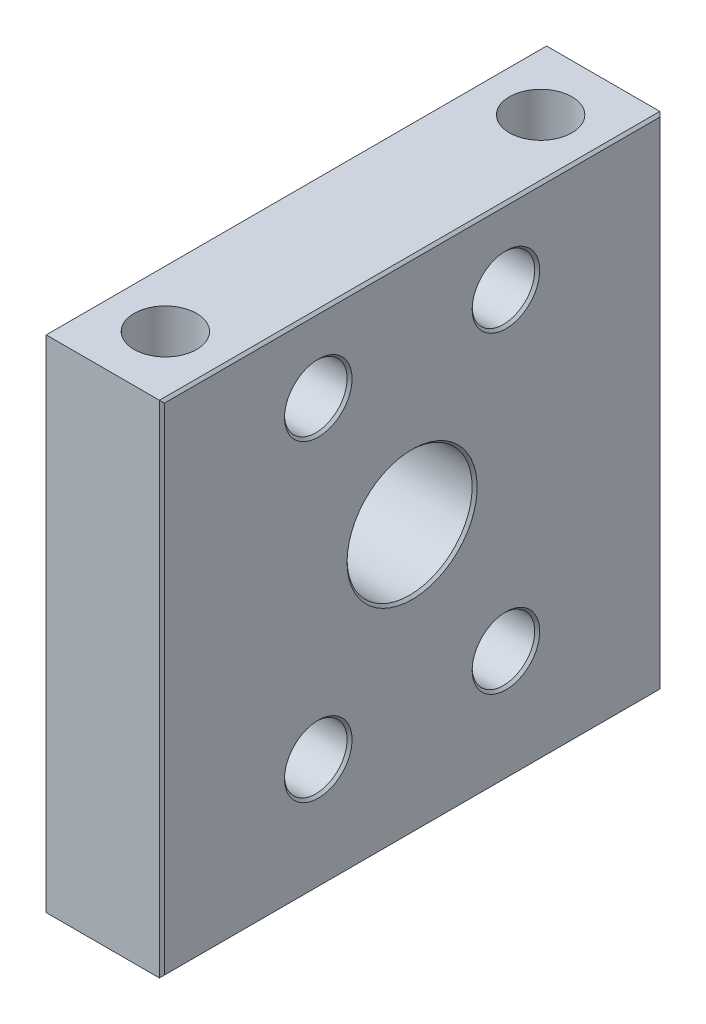
SolidWorks part; units mm, degrees
ref_plane "Front Plane" through (0, 0, 0) normal (0, 0, 1) x (1, 0, 0)
ref_plane "Top Plane" through (0, 0, 0) normal (0, 1, 0) x (1, 0, 0)
ref_plane "Right Plane" through (0, 0, 0) normal (1, 0, 0) x (0, 0, -1)
sketch "Sketch1" plane through (0, 0, 0) normal (0, 1, 0) x (1, 0, 0)
  line L1 (6.001, -25.4) -> (-6.001, -25.4)
  line L2 (6.001, -25.4) -> (6.001, 25.4)
  line L3 (6.001, 25.4) -> (-6.001, 25.4)
  line L4 (-6.001, -25.4) -> (-6.001, 25.4)
  line L5 (6.001, -25.4) -> (-6.001, 25.4) construction
  line L6 (6.001, 25.4) -> (-6.001, -25.4) construction
  circle A0 centre (0, 19.05) radius 3.175
  circle A1 centre (0, -19.05) radius 3.175
  point P0 (0, 0)
  dimension "D1" = 6.35
  dimension "D3" = 6.35
  dimension "D2" = 50.8
  dimension "D4" = 38.1
  dimension "D5" = 6.35
extrude "Boss-Extrude1" add sketch "Sketch1" along normal blind 50.8
sketch "Sketch2" plane through (6.001, 0, 0) normal (1, 0, 0) x (0, 0, -1)
  line L15 (-9.525, 43.18) -> (9.525, 43.18) construction
  line L16 (9.525, 43.18) -> (9.525, 11.43) construction
  line L17 (9.525, 11.43) -> (-9.525, 11.43) construction
  line L18 (-9.525, 11.43) -> (-9.525, 43.18) construction
  line L19 (-25.4, 50.8) -> (25.4, 50.8) construction
  line L20 (-9.525, 43.18) -> (9.525, 11.43) construction
  line L21 (9.525, 43.18) -> (-9.525, 11.43) construction
  circle A0 centre (-9.525, 43.18) radius 3.175
  circle A1 centre (9.525, 43.18) radius 3.175
  circle A2 centre (0, 27.305) radius 6.35
  circle A3 centre (-9.525, 11.43) radius 3.175
  circle A4 centre (9.525, 11.43) radius 3.175
  point P12 (0, 0)
  point P13 (0, 0)
  point P14 (0, 27.305)
  point P15 (0, 50.8)
  point P16 (0, 43.18)
  dimension "D1" = 6.35
  dimension "D2" = 12.7
  dimension "D3" = 19.05
  dimension "D4" = 7.62
  dimension "D5" = 31.75
extrude "Cut-Extrude1" cut sketch "Sketch2" against normal blind 50.8
chamfer "Chamfer1" distance 0.254 angle 45 18 edges at (-6.001, 25.4, -25.4) (-6.001, 50.8, 0) (-6.001, 25.4, 25.4) (-6.001, 0, 0) (-6.001, 43.18, 6.35) (-6.001, 43.18, -12.7) (-6.001, 27.305, -6.35) (-6.001, 11.43, 6.35) (-6.001, 11.43, -12.7) (6.001, 25.4, 25.4) (6.001, 50.8, 0) (6.001, 25.4, -25.4) (6.001, 0, 0) (6.001, 43.18, 6.35) (6.001, 43.18, -12.7) (6.001, 27.305, -6.35) (6.001, 11.43, 6.35) (6.001, 11.43, -12.7)
